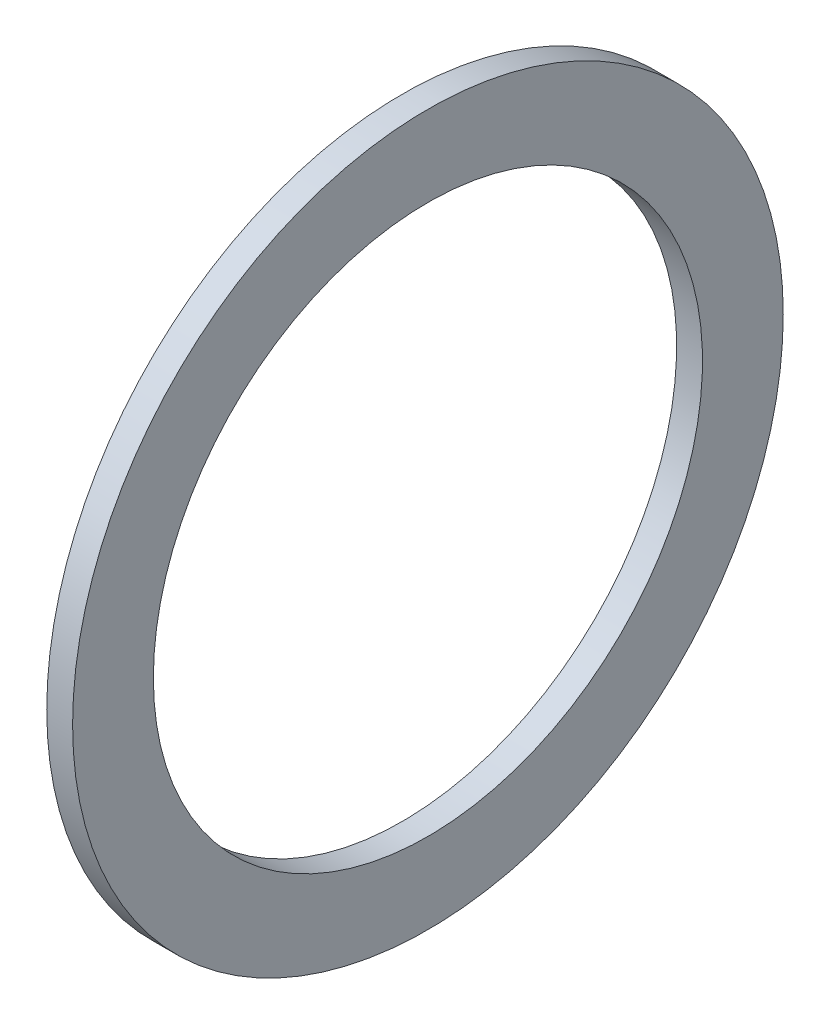
SolidWorks part; units mm, degrees
ref_plane "Front Plane" through (0, 0, 0) normal (0, 0, 1) x (1, 0, 0)
ref_plane "Top Plane" through (0, 0, 0) normal (0, 1, 0) x (1, 0, 0)
ref_plane "Right Plane" through (0, 0, 0) normal (1, 0, 0) x (0, 0, -1)
sketch "Sketch2" plane through (0, 0, 0) normal (0, 0, 1) x (1, 0, 0)
  line L0 (0, 0) -> (58.591, 0) construction
  line L2 (0, 0) -> (18.4, 0)
  line L3 (0, 0) -> (0, 2.5)
  line L4 (0, 2.5) -> (18.4, 2.5)
  line L5 (18.4, 0) -> (18.4, 2.5)
  line L6 (6, 2.5) -> (6, 6)
  line L11 (6, 6) -> (9.97, 6)
  line L16 (12.97, 6) -> (12.97, 3)
  line L17 (12.97, 3) -> (13.6304, 3)
  line L18 (13.6304, 3) -> (13.6304, 2.5)
  line L19 (13.6304, 2.5) -> (6, 2.5)
  line L22 (13.6304, 2.5) -> (16.1104, 2.5)
  line L23 (13.6304, 2.5) -> (13.6304, 4)
  line L24 (13.6304, 4) -> (16.1104, 4)
  line L25 (16.1104, 2.5) -> (16.1104, 4)
  line L27 (6, 6) -> (9.97, 6)
  line L28 (6, 6) -> (6, 9)
  line L29 (6, 9) -> (9.97, 9)
  line L30 (9.97, 6) -> (9.97, 9)
  line L31 (6, 9) -> (6, 8.25)
  line L32 (6, 8.25) -> (5, 8.25)
  line L33 (8.58, 22.001) -> (8.58, 12.476) construction
  line L34 (5, 12.476) -> (12.16, 12.476)
  line L35 (9.97, 9) -> (12.16, 9)
  line L36 (5, 7.5) -> (3, 7.5)
  line L37 (5, 8.25) -> (5, 12.476)
  line L38 (5, 7.5) -> (5, 14)
  line L39 (5, 14) -> (3, 14)
  line L40 (3, 7.5) -> (3, 14)
  line L41 (5, 22.001) -> (12.16, 22.001)
  line L42 (5, 22.001) -> (5, 30.1625)
  line L43 (5, 30.1625) -> (12.16, 30.1625)
  line L44 (12.16, 22.001) -> (12.16, 30.1625)
  line L49 (16.6304, 22.001) -> (16.6304, 7.5)
  line L51 (23.0104, 7.5) -> (23.0104, 6.5)
  line L54 (16.1104, 4) -> (13.6304, 4)
  line L56 (18.0304, 7.5) -> (23.0104, 7.5)
  line L57 (13.16, 22.001) -> (16.6304, 22.001)
  line L58 (16.1104, 3.5) -> (20.0104, 3.5)
  line L59 (29.9004, 14) -> (26.9004, 11)
  line L60 (4, 31.75) -> (18.0304, 31.75)
  line L61 (18.0304, 7.5) -> (23.0104, 7.5)
  line L62 (18.0304, 7.5) -> (18.0304, 12)
  line L63 (18.0304, 12) -> (23.0104, 12)
  line L64 (23.0104, 7.5) -> (23.0104, 12)
  line L65 (18.0304, 31.75) -> (18.0304, 12)
  line L66 (23.0104, 11) -> (26.9004, 11)
  line L67 (34.8004, 23) -> (31.3004, 19.5)
  line L68 (35.8004, 31) -> (38.7904, 33.99)
  line L69 (29.9004, 14) -> (29.9004, 15)
  line L70 (29.9004, 15) -> (22.9304, 15)
  line L71 (22.9304, 15) -> (21.0304, 15)
  line L72 (18.0304, 7.5) -> (16.6304, 7.5)
  line L73 (21.0304, 15) -> (21.0304, 43)
  line L74 (20.0304, 40) -> (10.0704, 40)
  line L75 (10.0704, 40) -> (4, 40)
  line L76 (21.0304, 43) -> (20.0304, 43)
  line L77 (22.9304, 15) -> (29.9004, 15)
  line L78 (22.9304, 15) -> (22.9304, 21)
  line L79 (22.9304, 21) -> (29.9004, 21)
  line L80 (29.9004, 15) -> (29.9004, 21)
  line L81 (10.0704, 40) -> (20.0304, 40)
  line L82 (10.0704, 40) -> (10.0704, 50)
  line L83 (10.0704, 50) -> (20.0304, 50)
  line L84 (20.0304, 40) -> (20.0304, 50)
  line L85 (4, 40) -> (4, 31.75)
  line L86 (12.97, 3) -> (12.97, 2.5)
  line L87 (31.3004, 19.5) -> (29.9004, 19.5)
  line L88 (21.51, 63.5) -> (21.51, 44)
  line L89 (21.51, 63.5) -> (25.9304, 63.5)
  line L90 (25.9304, 63.5) -> (25.9304, 25)
  line L91 (27.8304, 25) -> (25.9304, 25)
  line L92 (10.0704, 48) -> (9, 48)
  line L93 (9, 48) -> (9, 53.476)
  line L94 (9, 53.476) -> (20.0304, 53.476)
  line L95 (20.0304, 53.476) -> (20.0304, 50)
  line L96 (14.5152, 63.001) -> (14.5152, 53.476) construction
  line L97 (9, 63.001) -> (20.0304, 63.001)
  line L98 (9, 63.001) -> (9, 68.2625)
  line L99 (9, 68.2625) -> (20.0304, 68.2625)
  line L100 (20.0304, 63.001) -> (20.0304, 68.2625)
  line L101 (12.97, 6) -> (11.97, 6)
  line L102 (9, 42.5) -> (5, 42.5)
  line L103 (9, 42.5) -> (9, 55)
  line L104 (9, 55) -> (5, 55)
  line L105 (5, 42.5) -> (5, 55)
  line L106 (9.97, 6) -> (10.87, 6)
  line L107 (27.8304, 25) -> (34.8004, 25)
  line L108 (34.8004, 25) -> (34.8004, 23)
  line L109 (0, 0) -> (-2, 0)
  line L110 (0, 0) -> (0, 11)
  line L111 (27.8304, 25) -> (34.8004, 25)
  line L112 (27.8304, 25) -> (27.8304, 32.5)
  line L113 (27.8304, 32.5) -> (34.8004, 32.5)
  line L114 (34.8004, 25) -> (34.8004, 32.5)
  line L115 (35.8004, 31) -> (34.8004, 31)
  line L116 (27.8304, 32.5) -> (27.8304, 64.5)
  line L117 (21.1827, 74.025) -> (6.8477, 74.025)
  line L118 (6.8477, 74.025) -> (6.8477, 76.2)
  line L119 (38.7904, 47.29) -> (30.8304, 55.25)
  line L120 (0, 11) -> (-2, 11)
  line L121 (38.7904, 43.815) -> (30.8529, 43.815)
  line L123 (-4.8, 69.85) -> (1.55, 76.2)
  line L124 (38.7904, 47.29) -> (38.7904, 33.99)
  line L125 (-2, 0) -> (-2, 11)
  line L126 (38.7904, 37.465) -> (30.8529, 37.465)
  line L127 (30.8529, 43.815) -> (30.8529, 37.465)
  line L128 (6, 2.5) -> (6, 0)
  line L129 (0, 63.5) -> (0, 30)
  line L132 (5, 63.5) -> (0, 63.5)
  line L136 (-1.8, 30) -> (-11.76, 30)
  line L138 (-13.76, 25.4) -> (-2, 25.4)
  line L139 (-2, 25.4) -> (-2, 11.5)
  line L140 (27.8304, 64.5) -> (21.1827, 64.5)
  line L141 (-1.8, 30) -> (-11.76, 30)
  line L142 (-1.8, 30) -> (-1.8, 39)
  line L143 (-1.8, 39) -> (-11.76, 39)
  line L144 (-11.76, 30) -> (-11.76, 39)
  line L145 (21.1827, 64.5) -> (21.1827, 74.025)
  line L146 (-12.76, 37) -> (-12.76, 47.29)
  line L147 (-12.76, 37) -> (-11.76, 37)
  line L148 (30.8304, 55.25) -> (30.8304, 76.2)
  line L149 (11.97, 6) -> (11.97, 5.45)
  line L154 (-2, 11.5) -> (1, 11.5)
  line L155 (5, 60.6197) -> (24.05, 60.6197)
  line L160 (5, 60.6197) -> (5, 55.8572)
  line L161 (5, 55.8572) -> (24.05, 55.8572)
  line L166 (24.05, 60.6197) -> (24.05, 55.8572)
  line L167 (5, 60.6197) -> (24.05, 55.8572) construction
  line L172 (5, 55.8572) -> (24.05, 60.6197) construction
  line L173 (24.05, 62.2072) -> (25.9304, 62.2072)
  line L174 (11.97, 5.45) -> (10.87, 5.45)
  line L175 (10.87, 6) -> (10.87, 5.45)
  line L176 (24.05, 62.2072) -> (24.05, 54.2697)
  line L177 (24.05, 54.2697) -> (25.9304, 54.2697)
  line L178 (25.9304, 62.2072) -> (25.9304, 54.2697)
  line L179 (24.05, 62.2072) -> (25.9304, 54.2697) construction
  line L180 (24.05, 54.2697) -> (25.9304, 62.2072) construction
  line L181 (3, 19.6197) -> (15.7, 19.6197)
  line L182 (3, 19.6197) -> (3, 14.8572)
  line L183 (3, 14.8572) -> (15.7, 14.8572)
  line L184 (15.7, 19.6197) -> (15.7, 14.8572)
  line L185 (3, 19.6197) -> (15.7, 14.8572) construction
  line L186 (3, 14.8572) -> (15.7, 19.6197) construction
  line L187 (15.7, 21.2072) -> (16.6304, 21.2072)
  line L188 (15.7, 21.2072) -> (15.7, 13.2697)
  line L189 (15.7, 13.2697) -> (16.6304, 13.2697)
  line L190 (16.6304, 21.2072) -> (16.6304, 13.2697)
  line L191 (15.7, 21.2072) -> (16.6304, 13.2697) construction
  line L192 (15.7, 13.2697) -> (16.6304, 21.2072) construction
  line L193 (1, 11.5) -> (1, 6.5)
  line L194 (1, 6.5) -> (3, 6.5)
  line L195 (23.0104, 6.5) -> (20.0104, 3.5)
  line L196 (5, 63.5) -> (5, 42.5)
  line L197 (5, 42.5) -> (3, 42.5)
  line L198 (3, 42.5) -> (3, 6.5)
  line L199 (6, 0) -> (12.97, 0)
  line L200 (12.97, 0) -> (12.97, 2.5)
  line L201 (18.0304, 31.75) -> (18.0304, 35.875)
  line L202 (18.0304, 35.875) -> (21.0304, 35.875)
  line L203 (30.8304, 76.2) -> (6.8477, 76.2)
  line L204 (3.4027, 69.85) -> (7.8477, 69.85) construction
  line L205 (7.8477, 67.4687) -> (26.8977, 67.4688)
  line L206 (7.8477, 74.025) -> (7.8477, 64.5)
  line L207 (7.8477, 64.5) -> (-1.8, 64.5)
  line L208 (-1.8, 64.5) -> (-1.8, 39)
  line L209 (-12.76, 47.29) -> (-4.8, 55.25)
  line L210 (-4.8, 55.25) -> (-4.8, 69.85)
  line L211 (7.8477, 67.4687) -> (7.8477, 72.2313)
  line L212 (7.8477, 72.2313) -> (26.8977, 72.2313)
  line L213 (26.8977, 67.4688) -> (26.8977, 72.2313)
  line L214 (26.8977, 73.8187) -> (30.8304, 73.8187)
  line L215 (26.8977, 73.8187) -> (26.8977, 65.8813)
  line L216 (26.8977, 65.8813) -> (30.8304, 65.8813)
  line L217 (30.8304, 73.8187) -> (30.8304, 65.8813)
  line L218 (3.4027, 72.2313) -> (25.6277, 72.2313)
  line L219 (3.4027, 72.2313) -> (3.4027, 67.4687)
  line L220 (3.4027, 67.4687) -> (25.6277, 67.4687)
  line L221 (25.6277, 72.2313) -> (25.6277, 67.4687)
  line L222 (25.6277, 69.85) -> (21.1827, 69.85) construction
  line L223 (21.51, 44) -> (22.9304, 44)
  line L224 (22.9304, 44) -> (22.9304, 21)
  line L225 (13.6304, 4) -> (13.6304, 12.2697)
  line L226 (13.6304, 12.2697) -> (13.16, 12.2697)
  line L227 (13.16, 12.2697) -> (13.16, 22.001)
  line L228 (12.16, 9) -> (12.16, 12.476)
  line L229 (-1.8, 30) -> (0, 30)
  line L230 (9, 65.6317) -> (3.4027, 65.6317) construction
  line L231 (20.0304, 65.6317) -> (25.6277, 65.6317) construction
  line L232 (1.55, 76.2) -> (6.8477, 76.2)
  line L233 (-11.76, 30) -> (-13.76, 30)
  line L234 (-13.76, 30) -> (-13.76, 25.4)
  circle A0 centre (26.8804, 25.95) radius 0.95
  circle A1 centre (21.9804, 15.95) radius 0.95
  circle A2 centre (17.3304, 8.2) radius 0.7
  circle A3 centre (10.42, 6.45) radius 0.45
  circle A4 centre (-0.9, 30.9) radius 0.9
  point P7 (24.9902, 58.2385)
  point P131 (16.1652, 17.2385)
  point P135 (14.525, 58.2385)
  point P146 (9.35, 17.2385)
sketch "Sketch3" plane through (0, 0, 0) normal (0, 0, 1) x (1, 0, 0)
  line L0 (9, 42.5) -> (9, 55) construction
  line L1 (9, 55) -> (5, 55) construction
  line L2 (5, 42.5) -> (5, 55) construction
  line L3 (9, 42.5) -> (5, 42.5) construction
  line L4 (9, 42.5) -> (9, 55)
  line L5 (9, 55) -> (5, 55)
  line L6 (5, 42.5) -> (5, 55)
  line L7 (9, 42.5) -> (5, 42.5)
revolve "Revolve1" add sketch "Sketch3" angle 360 about L0
